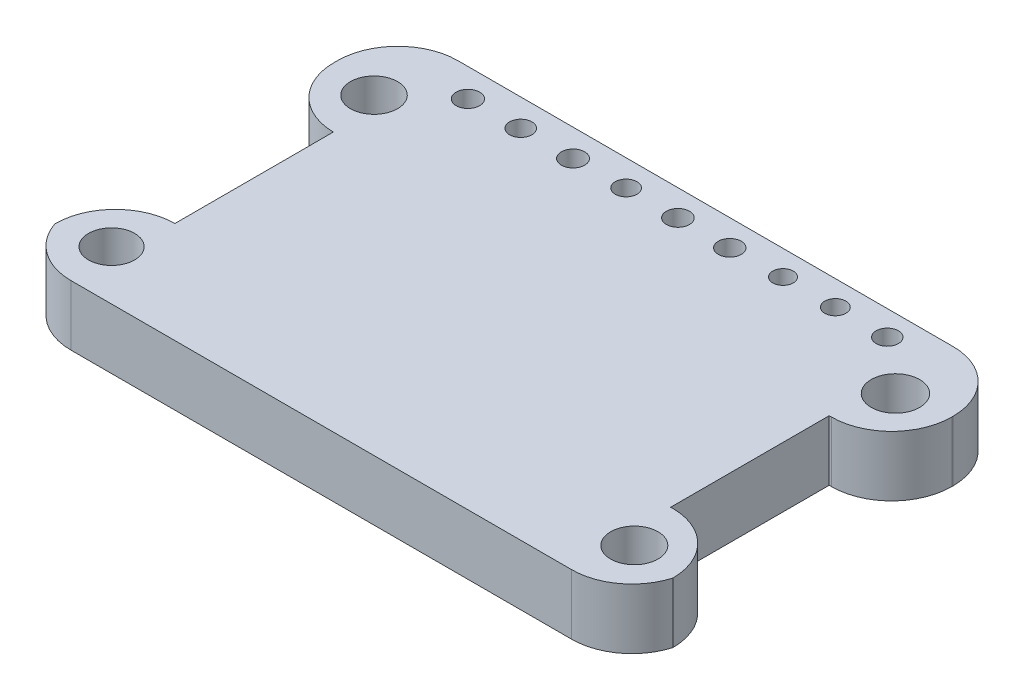
SolidWorks part; units mm, degrees
ref_plane "Front Plane" through (0, 0, 0) normal (0, 0, 1) x (1, 0, 0)
ref_plane "Top Plane" through (0, 0, 0) normal (0, 1, 0) x (1, 0, 0)
ref_plane "Right Plane" through (0, 0, 0) normal (1, 0, 0) x (0, 0, -1)
sketch "Sketch1" plane through (0, 0, 0) normal (0, 1, 0) x (1, 0, 0)
  line L1 (0, 0) -> (30.65, 0)
  line L2 (0, 0) -> (0, 19.11)
  line L3 (0, 19.11) -> (30.65, 19.11)
  line L4 (30.65, 0) -> (30.65, 19.11)
  dimension "D1" = 19.11
  dimension "D2" = 30.65
extrude "Boss-Extrude1" add sketch "Sketch1" along normal blind 3
sketch "Sketch4" plane through (0, 3, 0) normal (0, 1, 0) x (1, 0, 0)
  line L0 (30.65, 0) -> (30.65, 19.11) construction
  line L1 (27.5427, 13.0433) -> (30.65, 13.0433)
  line L2 (27.5427, 13.0433) -> (27.5427, 5.1554)
  line L3 (27.5427, 5.1554) -> (30.65, 5.1554)
  line L4 (30.65, 13.0433) -> (30.65, 5.1554)
extrude "Cut-Extrude1" cut sketch "Sketch4" against normal through all
fillet "Fillet5" radius 3 2 edges at (30.65, 1.5, -13.0433) (30.65, 1.5, -5.1554)
sketch "Sketch5" plane through (0, 3, 0) normal (0, 1, 0) x (1, 0, 0)
  line L0 (0, 19.11) -> (0, 0) construction
  line L1 (2.9739, 5.0499) -> (0, 5.0499)
  line L2 (2.9739, 5.0499) -> (2.9739, 12.9338)
  line L3 (2.9739, 12.9338) -> (0, 12.9338)
  line L4 (0, 5.0499) -> (0, 12.9338)
extrude "Cut-Extrude2" cut sketch "Sketch5" against normal through all
fillet "Fillet6" radius 3 2 edges at (0, 1.5, -12.9338) (0, 1.5, -5.0499)
fillet "Fillet7" radius 3 4 edges at (30.65, 1.5, -19.11) (0, 1.5, 0) (30.65, 1.5, 0) (0, 1.5, -19.11)
sketch "Sketch6" plane through (0, 3, 0) normal (0, 1, 0) x (1, 0, 0)
  circle A0 centre (2.3977, 2.4726) radius 1.1475
  circle A1 centre (2.3977, 15.5346) radius 1.1718
  circle A2 centre (28.2334, 15.6521) radius 1.2048
  circle A3 centre (28.284, 2.6043) radius 1.1798
extrude "Cut-Extrude3" cut sketch "Sketch6" against normal through all
sketch "Sketch7" plane through (0, 3, 0) normal (0, 1, 0) x (1, 0, 0)
  circle A0 centre (25.6037, 17.875) radius 0.5534
  circle A1 centre (23.0183, 17.875) radius 0.5262
  circle A2 centre (20.4146, 17.875) radius 0.5116
  circle A3 centre (17.8322, 17.8081) radius 0.5705
  circle A4 centre (15.2506, 17.8081) radius 0.5749
  circle A5 centre (12.673, 17.8081) radius 0.5423
  circle A6 centre (10.081, 17.7568) radius 0.5795
  circle A7 centre (7.4792, 17.7568) radius 0.558
  circle A8 centre (4.8957, 17.7105) radius 0.5862
extrude "Cut-Extrude4" cut sketch "Sketch7" against normal through all
